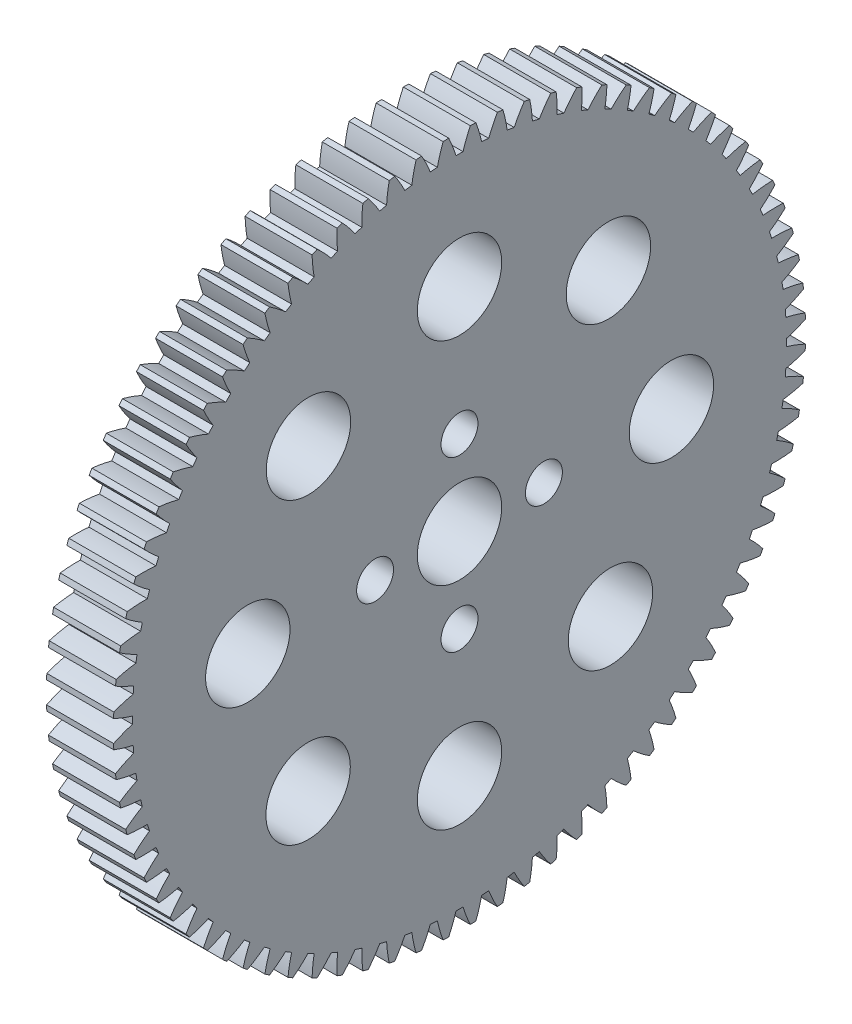
SolidWorks part; units mm, degrees
material "2024 Alloy"
ref_plane "Front Plane" through (0, 0, 0) normal (0, 0, 1) x (1, 0, 0)
ref_plane "Top Plane" through (0, 0, 0) normal (0, 1, 0) x (1, 0, 0)
ref_plane "Right Plane" through (0, 0, 0) normal (1, 0, 0) x (0, 0, -1)
ref_plane "Plane1" through (0, 0, 0) normal (-1, 0, 0) x (0, -1, 0)
ref_axis "Axis1" through (-3.4925, 0, 0) along (1, 0, 0)
sketch "Sketch1" plane through (0, 0, 0) normal (-1, 0, 0) x (0, -1, 0)
  circle A0 centre (0, 0) radius 4
  circle A1 centre (0, 8) radius 1.75
  circle A2 centre (-20.084, 0) radius 4
  circle A3 centre (20.0633, 0) radius 4
  circle A4 centre (0, -20.084) radius 4
  circle A5 centre (0, 20.0633) radius 4
  circle A6 centre (-14.3663, -14.1126) radius 4
  circle A7 centre (14.142, -14.3069) radius 4
  circle A8 centre (14.1351, 14.3483) radius 4
  circle A9 centre (-14.1597, 14.315) radius 4
  circle A10 centre (-8, 0) radius 1.75
  circle A11 centre (8, 0) radius 1.75
  circle A12 centre (0, -8) radius 1.75
  arc A13 (-32.5405, -4.1179) -> (-30.6681, -4.5175) centre (-28.9403, 8.1654) ccw
  arc A14 (-30.6681, -4.5175) -> (-30.563, -5.1806) centre (0, 0) ccw
  arc A15 (-30.563, -5.1806) -> (-32.2203, -6.1392) centre (-25.0006, -16.7088) ccw
  arc A16 (-32.2203, -6.1392) -> (-32.1171, -6.6583) centre (0, 0) ccw
  arc A17 (-32.1171, -6.6583) -> (-30.2191, -6.9097) centre (-29.4917, 5.8696) ccw
  arc A18 (-30.2191, -6.9097) -> (-30.0624, -7.5626) centre (0, 0) ccw
  arc A19 (-30.0624, -7.5626) -> (-31.6393, -8.6483) centre (-23.6126, -18.6188) ccw
  arc A20 (-31.6393, -8.6483) -> (-31.4957, -9.1576) centre (0, 0) ccw
  arc A21 (-31.4957, -9.1576) -> (-29.5838, -9.2594) centre (-29.8613, 3.5376) ccw
  arc A22 (-29.5838, -9.2594) -> (-29.3763, -9.8979) centre (0, 0) ccw
  arc A23 (-29.3763, -9.8979) -> (-30.8633, -11.104) centre (-22.079, -20.414) ccw
  arc A24 (-30.8633, -11.104) -> (-30.6801, -11.6005) centre (0, 0) ccw
  arc A25 (-30.6801, -11.6005) -> (-28.7661, -11.552) centre (-30.0469, 1.1838) ccw
  arc A26 (-28.7661, -11.552) -> (-28.5092, -12.1723) centre (0, 0) ccw
  arc A27 (-28.5092, -12.1723) -> (-29.8969, -13.4913) centre (-20.4093, -22.0834) ccw
  arc A28 (-29.8969, -13.4913) -> (-29.6753, -13.9719) centre (0, 0) ccw
  arc A29 (-29.6753, -13.9719) -> (-27.7711, -13.7733) centre (-30.0471, -1.1773) ccw
  arc A30 (-27.7711, -13.7733) -> (-27.4663, -14.3715) centre (0, 0) ccw
  arc A31 (-27.4663, -14.3715) -> (-28.7462, -15.7954) centre (-18.6137, -23.6166) ccw
  arc A32 (-28.7462, -15.7954) -> (-28.4876, -16.2571) centre (0, 0) ccw
  arc A33 (-28.4876, -16.2571) -> (-26.6048, -15.9097) centre (-29.8621, -3.5311) ccw
  arc A34 (-26.6048, -15.9097) -> (-26.254, -16.4822) centre (0, 0) ccw
  arc A35 (-26.254, -16.4822) -> (-27.4183, -18.0021) centre (-16.7034, -25.0042) ccw
  arc A36 (-27.4183, -18.0021) -> (-27.1243, -18.4421) centre (0, 0) ccw
  arc A37 (-27.1243, -18.4421) -> (-25.2746, -17.9481) centre (-29.493, -5.8632) ccw
  arc A38 (-25.2746, -17.9481) -> (-24.8799, -18.4913) centre (0, 0) ccw
  arc A39 (-24.8799, -18.4913) -> (-25.9214, -20.0978) centre (-14.6901, -26.2377) ccw
  arc A40 (-25.9214, -20.0978) -> (-25.5937, -20.5134) centre (0, 0) ccw
  arc A41 (-25.5937, -20.5134) -> (-23.7885, -19.8758) centre (-28.9421, -8.1591) ccw
  arc A42 (-23.7885, -19.8758) -> (-23.3524, -20.3863) centre (0, 0) ccw
  arc A43 (-23.3524, -20.3863) -> (-24.2646, -22.0696) centre (-12.5862, -27.3094) ccw
  arc A44 (-24.2646, -22.0696) -> (-23.9054, -22.4582) centre (0, 0) ccw
  arc A45 (-23.9054, -22.4582) -> (-22.1557, -21.6809) centre (-28.2127, -10.4047) ccw
  arc A46 (-22.1557, -21.6809) -> (-21.6809, -22.1557) centre (0, 0) ccw
  arc A47 (-21.6809, -22.1557) -> (-22.4582, -23.9054) centre (-10.4047, -28.2127) ccw
  arc A48 (-22.4582, -23.9054) -> (-22.0696, -24.2646) centre (0, 0) ccw
  arc A49 (-22.0696, -24.2646) -> (-20.3863, -23.3524) centre (-27.3094, -12.5862) ccw
  arc A50 (-20.3863, -23.3524) -> (-19.8758, -23.7885) centre (0, 0) ccw
  arc A51 (-19.8758, -23.7885) -> (-20.5134, -25.5937) centre (-8.1591, -28.9421) ccw
  arc A52 (-20.5134, -25.5937) -> (-20.0978, -25.9214) centre (0, 0) ccw
  arc A53 (-20.0978, -25.9214) -> (-18.4913, -24.8799) centre (-26.2377, -14.6901) ccw
  arc A54 (-18.4913, -24.8799) -> (-17.9481, -25.2746) centre (0, 0) ccw
  arc A55 (-17.9481, -25.2746) -> (-18.4421, -27.1243) centre (-5.8632, -29.493) ccw
  arc A56 (-18.4421, -27.1243) -> (-18.0021, -27.4183) centre (0, 0) ccw
  arc A57 (-18.0021, -27.4183) -> (-16.4822, -26.254) centre (-25.0042, -16.7034) ccw
  arc A58 (-16.4822, -26.254) -> (-15.9097, -26.6048) centre (0, 0) ccw
  arc A59 (-15.9097, -26.6048) -> (-16.2571, -28.4876) centre (-3.5311, -29.8621) ccw
  arc A60 (-16.2571, -28.4876) -> (-15.7954, -28.7462) centre (0, 0) ccw
  arc A61 (-15.7954, -28.7462) -> (-14.3715, -27.4663) centre (-23.6166, -18.6137) ccw
  arc A62 (-14.3715, -27.4663) -> (-13.7733, -27.7711) centre (0, 0) ccw
  arc A63 (-13.7733, -27.7711) -> (-13.9719, -29.6753) centre (-1.1773, -30.0471) ccw
  arc A64 (-13.9719, -29.6753) -> (-13.4913, -29.8969) centre (0, 0) ccw
  arc A65 (-13.4913, -29.8969) -> (-12.1723, -28.5092) centre (-22.0834, -20.4093) ccw
  arc A66 (-12.1723, -28.5092) -> (-11.552, -28.7661) centre (0, 0) ccw
  arc A67 (-11.552, -28.7661) -> (-11.6005, -30.6801) centre (1.1838, -30.0469) ccw
  arc A68 (-11.6005, -30.6801) -> (-11.104, -30.8633) centre (0, 0) ccw
  arc A69 (-11.104, -30.8633) -> (-9.8979, -29.3763) centre (-20.414, -22.079) ccw
  arc A70 (-9.8979, -29.3763) -> (-9.2594, -29.5838) centre (0, 0) ccw
  arc A71 (-9.2594, -29.5838) -> (-9.1576, -31.4957) centre (3.5376, -29.8613) ccw
  arc A72 (-9.1576, -31.4957) -> (-8.6483, -31.6393) centre (0, 0) ccw
  arc A73 (-8.6483, -31.6393) -> (-7.5626, -30.0624) centre (-18.6188, -23.6126) ccw
  arc A74 (-7.5626, -30.0624) -> (-6.9097, -30.2191) centre (0, 0) ccw
  arc A75 (-6.9097, -30.2191) -> (-6.6583, -32.1171) centre (5.8696, -29.4917) ccw
  arc A76 (-6.6583, -32.1171) -> (-6.1392, -32.2203) centre (0, 0) ccw
  arc A77 (-6.1392, -32.2203) -> (-5.1806, -30.563) centre (-16.7088, -25.0006) ccw
  arc A78 (-5.1806, -30.563) -> (-4.5175, -30.6681) centre (0, 0) ccw
  arc A79 (-4.5175, -30.6681) -> (-4.1179, -32.5405) centre (8.1654, -28.9403) ccw
  arc A80 (-4.1179, -32.5405) -> (-3.5923, -32.6027) centre (0, 0) ccw
  arc A81 (-3.5923, -32.6027) -> (-2.7667, -30.8753) centre (-14.6958, -26.2345) ccw
  arc A82 (-2.7667, -30.8753) -> (-2.0973, -30.928) centre (0, 0) ccw
  arc A83 (-2.0973, -30.928) -> (-1.5521, -32.7633) centre (10.4109, -28.2104) ccw
  arc A84 (-1.5521, -32.7633) -> (-1.0233, -32.784) centre (0, 0) ccw
  arc A85 (-1.0233, -32.784) -> (-0.3357, -30.9972) centre (-12.5921, -27.3066) ccw
  arc A86 (-0.3357, -30.9972) -> (0.3357, -30.9972) centre (0, 0) ccw
  arc A87 (0.3357, -30.9972) -> (1.0233, -32.784) centre (12.5921, -27.3066) ccw
  arc A88 (1.0233, -32.784) -> (1.5521, -32.7633) centre (0, 0) ccw
  arc A89 (1.5521, -32.7633) -> (2.0973, -30.928) centre (-10.4109, -28.2104) ccw
  arc A90 (2.0973, -30.928) -> (2.7667, -30.8753) centre (0, 0) ccw
  arc A91 (2.7667, -30.8753) -> (3.5923, -32.6027) centre (14.6958, -26.2345) ccw
  arc A92 (3.5923, -32.6027) -> (4.1179, -32.5405) centre (0, 0) ccw
  arc A93 (4.1179, -32.5405) -> (4.5175, -30.6681) centre (-8.1654, -28.9403) ccw
  arc A94 (4.5175, -30.6681) -> (5.1806, -30.563) centre (0, 0) ccw
  arc A95 (5.1806, -30.563) -> (6.1392, -32.2203) centre (16.7088, -25.0006) ccw
  arc A96 (6.1392, -32.2203) -> (6.6583, -32.1171) centre (0, 0) ccw
  arc A97 (6.6583, -32.1171) -> (6.9097, -30.2191) centre (-5.8696, -29.4917) ccw
  arc A98 (6.9097, -30.2191) -> (7.5626, -30.0624) centre (0, 0) ccw
  arc A99 (7.5626, -30.0624) -> (8.6483, -31.6393) centre (18.6188, -23.6126) ccw
  arc A100 (8.6483, -31.6393) -> (9.1576, -31.4957) centre (0, 0) ccw
  arc A101 (9.1576, -31.4957) -> (9.2594, -29.5838) centre (-3.5376, -29.8613) ccw
  arc A102 (9.2594, -29.5838) -> (9.8979, -29.3763) centre (0, 0) ccw
  arc A103 (9.8979, -29.3763) -> (11.104, -30.8633) centre (20.414, -22.079) ccw
  arc A104 (11.104, -30.8633) -> (11.6005, -30.6801) centre (0, 0) ccw
  arc A105 (11.6005, -30.6801) -> (11.552, -28.7661) centre (-1.1838, -30.0469) ccw
  arc A106 (11.552, -28.7661) -> (12.1723, -28.5092) centre (0, 0) ccw
  arc A107 (12.1723, -28.5092) -> (13.4913, -29.8969) centre (22.0834, -20.4093) ccw
  arc A108 (13.4913, -29.8969) -> (13.9719, -29.6753) centre (0, 0) ccw
  arc A109 (13.9719, -29.6753) -> (13.7733, -27.7711) centre (1.1773, -30.0471) ccw
  arc A110 (13.7733, -27.7711) -> (14.3715, -27.4663) centre (0, 0) ccw
  arc A111 (14.3715, -27.4663) -> (15.7954, -28.7462) centre (23.6166, -18.6137) ccw
  arc A112 (15.7954, -28.7462) -> (16.2571, -28.4876) centre (0, 0) ccw
  arc A113 (16.2571, -28.4876) -> (15.9097, -26.6048) centre (3.5311, -29.8621) ccw
  arc A114 (15.9097, -26.6048) -> (16.4822, -26.254) centre (0, 0) ccw
  arc A115 (16.4822, -26.254) -> (18.0021, -27.4183) centre (25.0042, -16.7034) ccw
  arc A116 (18.0021, -27.4183) -> (18.4421, -27.1243) centre (0, 0) ccw
  arc A117 (18.4421, -27.1243) -> (17.9481, -25.2746) centre (5.8632, -29.493) ccw
  arc A118 (17.9481, -25.2746) -> (18.4913, -24.8799) centre (0, 0) ccw
  arc A119 (18.4913, -24.8799) -> (20.0978, -25.9214) centre (26.2377, -14.6901) ccw
  arc A120 (20.0978, -25.9214) -> (20.5134, -25.5937) centre (0, 0) ccw
  arc A121 (20.5134, -25.5937) -> (19.8758, -23.7885) centre (8.1591, -28.9421) ccw
  arc A122 (19.8758, -23.7885) -> (20.3863, -23.3524) centre (0, 0) ccw
  arc A123 (20.3863, -23.3524) -> (22.0696, -24.2646) centre (27.3094, -12.5862) ccw
  arc A124 (22.0696, -24.2646) -> (22.4582, -23.9054) centre (0, 0) ccw
  arc A125 (22.4582, -23.9054) -> (21.6809, -22.1557) centre (10.4047, -28.2127) ccw
  arc A126 (21.6809, -22.1557) -> (22.1557, -21.6809) centre (0, 0) ccw
  arc A127 (22.1557, -21.6809) -> (23.9054, -22.4582) centre (28.2127, -10.4047) ccw
  arc A128 (23.9054, -22.4582) -> (24.2646, -22.0696) centre (0, 0) ccw
  arc A129 (24.2646, -22.0696) -> (23.3524, -20.3863) centre (12.5862, -27.3094) ccw
  arc A130 (23.3524, -20.3863) -> (23.7885, -19.8758) centre (0, 0) ccw
  arc A131 (23.7885, -19.8758) -> (25.5937, -20.5134) centre (28.9421, -8.1591) ccw
  arc A132 (25.5937, -20.5134) -> (25.9214, -20.0978) centre (0, 0) ccw
  arc A133 (25.9214, -20.0978) -> (24.8799, -18.4913) centre (14.6901, -26.2377) ccw
  arc A134 (24.8799, -18.4913) -> (25.2746, -17.9481) centre (0, 0) ccw
  arc A135 (25.2746, -17.9481) -> (27.1243, -18.4421) centre (29.493, -5.8632) ccw
  arc A136 (27.1243, -18.4421) -> (27.4183, -18.0021) centre (0, 0) ccw
  arc A137 (27.4183, -18.0021) -> (26.254, -16.4822) centre (16.7034, -25.0042) ccw
  arc A138 (26.254, -16.4822) -> (26.6048, -15.9097) centre (0, 0) ccw
  arc A139 (26.6048, -15.9097) -> (28.4876, -16.2571) centre (29.8621, -3.5311) ccw
  arc A140 (28.4876, -16.2571) -> (28.7462, -15.7954) centre (0, 0) ccw
  arc A141 (28.7462, -15.7954) -> (27.4663, -14.3715) centre (18.6137, -23.6166) ccw
  arc A142 (27.4663, -14.3715) -> (27.7711, -13.7733) centre (0, 0) ccw
  arc A143 (27.7711, -13.7733) -> (29.6753, -13.9719) centre (30.0471, -1.1773) ccw
  arc A144 (29.6753, -13.9719) -> (29.8969, -13.4913) centre (0, 0) ccw
  arc A145 (29.8969, -13.4913) -> (28.5092, -12.1723) centre (20.4093, -22.0834) ccw
  arc A146 (28.5092, -12.1723) -> (28.7661, -11.552) centre (0, 0) ccw
  arc A147 (28.7661, -11.552) -> (30.6801, -11.6005) centre (30.0469, 1.1838) ccw
  arc A148 (30.6801, -11.6005) -> (30.8633, -11.104) centre (0, 0) ccw
  arc A149 (30.8633, -11.104) -> (29.3763, -9.8979) centre (22.079, -20.414) ccw
  arc A150 (29.3763, -9.8979) -> (29.5838, -9.2594) centre (0, 0) ccw
  arc A151 (29.5838, -9.2594) -> (31.4957, -9.1576) centre (29.8613, 3.5376) ccw
  arc A152 (31.4957, -9.1576) -> (31.6393, -8.6483) centre (0, 0) ccw
  arc A153 (31.6393, -8.6483) -> (30.0624, -7.5626) centre (23.6126, -18.6188) ccw
  arc A154 (30.0624, -7.5626) -> (30.2191, -6.9097) centre (0, 0) ccw
  arc A155 (30.2191, -6.9097) -> (32.1171, -6.6583) centre (29.4917, 5.8696) ccw
  arc A156 (32.1171, -6.6583) -> (32.2203, -6.1392) centre (0, 0) ccw
  arc A157 (32.2203, -6.1392) -> (30.563, -5.1806) centre (25.0006, -16.7088) ccw
  arc A158 (30.563, -5.1806) -> (30.6681, -4.5175) centre (0, 0) ccw
  arc A159 (30.6681, -4.5175) -> (32.5405, -4.1179) centre (28.9403, 8.1654) ccw
  arc A160 (32.5405, -4.1179) -> (32.6027, -3.5923) centre (0, 0) ccw
  arc A161 (32.6027, -3.5923) -> (30.8753, -2.7667) centre (26.2345, -14.6958) ccw
  arc A162 (30.8753, -2.7667) -> (30.928, -2.0973) centre (0, 0) ccw
  arc A163 (30.928, -2.0973) -> (32.7633, -1.5521) centre (28.2104, 10.4109) ccw
  arc A164 (32.7633, -1.5521) -> (32.784, -1.0233) centre (0, 0) ccw
  arc A165 (32.784, -1.0233) -> (30.9972, -0.3357) centre (27.3066, -12.5921) ccw
  arc A166 (30.9972, -0.3357) -> (30.9972, 0.3357) centre (0, 0) ccw
  arc A167 (30.9972, 0.3357) -> (32.784, 1.0233) centre (27.3066, 12.5921) ccw
  arc A168 (32.784, 1.0233) -> (32.7633, 1.5521) centre (0, 0) ccw
  arc A169 (32.7633, 1.5521) -> (30.928, 2.0973) centre (28.2104, -10.4109) ccw
  arc A170 (30.928, 2.0973) -> (30.8753, 2.7667) centre (0, 0) ccw
  arc A171 (30.8753, 2.7667) -> (32.6027, 3.5923) centre (26.2345, 14.6958) ccw
  arc A172 (32.6027, 3.5923) -> (32.5405, 4.1179) centre (0, 0) ccw
  arc A173 (32.5405, 4.1179) -> (30.6681, 4.5175) centre (28.9403, -8.1654) ccw
  arc A174 (30.6681, 4.5175) -> (30.563, 5.1806) centre (0, 0) ccw
  arc A175 (30.563, 5.1806) -> (32.2203, 6.1392) centre (25.0006, 16.7088) ccw
  arc A176 (32.2203, 6.1392) -> (32.1171, 6.6583) centre (0, 0) ccw
  arc A177 (32.1171, 6.6583) -> (30.2191, 6.9097) centre (29.4917, -5.8696) ccw
  arc A178 (30.2191, 6.9097) -> (30.0624, 7.5626) centre (0, 0) ccw
  arc A179 (30.0624, 7.5626) -> (31.6393, 8.6483) centre (23.6126, 18.6188) ccw
  arc A180 (31.6393, 8.6483) -> (31.4957, 9.1576) centre (0, 0) ccw
  arc A181 (31.4957, 9.1576) -> (29.5838, 9.2594) centre (29.8613, -3.5376) ccw
  arc A182 (29.5838, 9.2594) -> (29.3763, 9.8979) centre (0, 0) ccw
  arc A183 (29.3763, 9.8979) -> (30.8633, 11.104) centre (22.079, 20.414) ccw
  arc A184 (30.8633, 11.104) -> (30.6801, 11.6005) centre (0, 0) ccw
  arc A185 (30.6801, 11.6005) -> (28.7661, 11.552) centre (30.0469, -1.1838) ccw
  arc A186 (28.7661, 11.552) -> (28.5092, 12.1723) centre (0, 0) ccw
  arc A187 (28.5092, 12.1723) -> (29.8969, 13.4913) centre (20.4093, 22.0834) ccw
  arc A188 (29.8969, 13.4913) -> (29.6753, 13.9719) centre (0, 0) ccw
  arc A189 (29.6753, 13.9719) -> (27.7711, 13.7733) centre (30.0471, 1.1773) ccw
  arc A190 (27.7711, 13.7733) -> (27.4663, 14.3715) centre (0, 0) ccw
  arc A191 (27.4663, 14.3715) -> (28.7462, 15.7954) centre (18.6137, 23.6166) ccw
  arc A192 (28.7462, 15.7954) -> (28.4876, 16.2571) centre (0, 0) ccw
  arc A193 (28.4876, 16.2571) -> (26.6048, 15.9097) centre (29.8621, 3.5311) ccw
  arc A194 (26.6048, 15.9097) -> (26.254, 16.4822) centre (0, 0) ccw
  arc A195 (26.254, 16.4822) -> (27.4183, 18.0021) centre (16.7034, 25.0042) ccw
  arc A196 (27.4183, 18.0021) -> (27.1243, 18.4421) centre (0, 0) ccw
  arc A197 (27.1243, 18.4421) -> (25.2746, 17.9481) centre (29.493, 5.8632) ccw
  arc A198 (25.2746, 17.9481) -> (24.8799, 18.4913) centre (0, 0) ccw
  arc A199 (24.8799, 18.4913) -> (25.9214, 20.0978) centre (14.6901, 26.2377) ccw
  arc A200 (25.9214, 20.0978) -> (25.5937, 20.5134) centre (0, 0) ccw
  arc A201 (25.5937, 20.5134) -> (23.7885, 19.8758) centre (28.9421, 8.1591) ccw
  arc A202 (23.7885, 19.8758) -> (23.3524, 20.3863) centre (0, 0) ccw
  arc A203 (23.3524, 20.3863) -> (24.2646, 22.0696) centre (12.5862, 27.3094) ccw
  arc A204 (24.2646, 22.0696) -> (23.9054, 22.4582) centre (0, 0) ccw
  arc A205 (23.9054, 22.4582) -> (22.1557, 21.6809) centre (28.2127, 10.4047) ccw
  arc A206 (22.1557, 21.6809) -> (21.6809, 22.1557) centre (0, 0) ccw
  arc A207 (21.6809, 22.1557) -> (22.4582, 23.9054) centre (10.4047, 28.2127) ccw
  arc A208 (22.4582, 23.9054) -> (22.0696, 24.2646) centre (0, 0) ccw
  arc A209 (22.0696, 24.2646) -> (20.3863, 23.3524) centre (27.3094, 12.5862) ccw
  arc A210 (20.3863, 23.3524) -> (19.8758, 23.7885) centre (0, 0) ccw
  arc A211 (19.8758, 23.7885) -> (20.5134, 25.5937) centre (8.1591, 28.9421) ccw
  arc A212 (20.5134, 25.5937) -> (20.0978, 25.9214) centre (0, 0) ccw
  arc A213 (20.0978, 25.9214) -> (18.4913, 24.8799) centre (26.2377, 14.6901) ccw
  arc A214 (18.4913, 24.8799) -> (17.9481, 25.2746) centre (0, 0) ccw
  arc A215 (17.9481, 25.2746) -> (18.4421, 27.1243) centre (5.8632, 29.493) ccw
  arc A216 (18.4421, 27.1243) -> (18.0021, 27.4183) centre (0, 0) ccw
  arc A217 (18.0021, 27.4183) -> (16.4822, 26.254) centre (25.0042, 16.7034) ccw
  arc A218 (16.4822, 26.254) -> (15.9097, 26.6048) centre (0, 0) ccw
  arc A219 (15.9097, 26.6048) -> (16.2571, 28.4876) centre (3.5311, 29.8621) ccw
  arc A220 (16.2571, 28.4876) -> (15.7954, 28.7462) centre (0, 0) ccw
  arc A221 (15.7954, 28.7462) -> (14.3715, 27.4663) centre (23.6166, 18.6137) ccw
  arc A222 (14.3715, 27.4663) -> (13.7733, 27.7711) centre (0, 0) ccw
  arc A223 (13.7733, 27.7711) -> (13.9719, 29.6753) centre (1.1773, 30.0471) ccw
  arc A224 (13.9719, 29.6753) -> (13.4913, 29.8969) centre (0, 0) ccw
  arc A225 (13.4913, 29.8969) -> (12.1723, 28.5092) centre (22.0834, 20.4093) ccw
  arc A226 (12.1723, 28.5092) -> (11.552, 28.7661) centre (0, 0) ccw
  arc A227 (11.552, 28.7661) -> (11.6005, 30.6801) centre (-1.1838, 30.0469) ccw
  arc A228 (11.6005, 30.6801) -> (11.104, 30.8633) centre (0, 0) ccw
  arc A229 (11.104, 30.8633) -> (9.8979, 29.3763) centre (20.414, 22.079) ccw
  arc A230 (9.8979, 29.3763) -> (9.2594, 29.5838) centre (0, 0) ccw
  arc A231 (9.2594, 29.5838) -> (9.1576, 31.4957) centre (-3.5376, 29.8613) ccw
  arc A232 (9.1576, 31.4957) -> (8.6483, 31.6393) centre (0, 0) ccw
  arc A233 (8.6483, 31.6393) -> (7.5626, 30.0624) centre (18.6188, 23.6126) ccw
  arc A234 (7.5626, 30.0624) -> (6.9097, 30.2191) centre (0, 0) ccw
  arc A235 (6.9097, 30.2191) -> (6.6583, 32.1171) centre (-5.8696, 29.4917) ccw
  arc A236 (6.6583, 32.1171) -> (6.1392, 32.2203) centre (0, 0) ccw
  arc A237 (6.1392, 32.2203) -> (5.1806, 30.563) centre (16.7088, 25.0006) ccw
  arc A238 (5.1806, 30.563) -> (4.5175, 30.6681) centre (0, 0) ccw
  arc A239 (4.5175, 30.6681) -> (4.1179, 32.5405) centre (-8.1654, 28.9403) ccw
  arc A240 (4.1179, 32.5405) -> (3.5923, 32.6027) centre (0, 0) ccw
  arc A241 (3.5923, 32.6027) -> (2.7667, 30.8753) centre (14.6958, 26.2345) ccw
  arc A242 (2.7667, 30.8753) -> (2.0973, 30.928) centre (0, 0) ccw
  arc A243 (2.0973, 30.928) -> (1.5521, 32.7633) centre (-10.4109, 28.2104) ccw
  arc A244 (1.5521, 32.7633) -> (1.0233, 32.784) centre (0, 0) ccw
  arc A245 (1.0233, 32.784) -> (0.3357, 30.9972) centre (12.5921, 27.3066) ccw
  arc A246 (0.3357, 30.9972) -> (-0.3357, 30.9972) centre (0, 0) ccw
  arc A247 (-0.3357, 30.9972) -> (-1.0233, 32.784) centre (-12.5921, 27.3066) ccw
  arc A248 (-1.0233, 32.784) -> (-1.5521, 32.7633) centre (0, 0) ccw
  arc A249 (-1.5521, 32.7633) -> (-2.0973, 30.928) centre (10.4109, 28.2104) ccw
  arc A250 (-2.0973, 30.928) -> (-2.7667, 30.8753) centre (0, 0) ccw
  arc A251 (-2.7667, 30.8753) -> (-3.5923, 32.6027) centre (-14.6958, 26.2345) ccw
  arc A252 (-3.5923, 32.6027) -> (-4.1179, 32.5405) centre (0, 0) ccw
  arc A253 (-4.1179, 32.5405) -> (-4.5175, 30.6681) centre (8.1654, 28.9403) ccw
  arc A254 (-4.5175, 30.6681) -> (-5.1806, 30.563) centre (0, 0) ccw
  arc A255 (-5.1806, 30.563) -> (-6.1392, 32.2203) centre (-16.7088, 25.0006) ccw
  arc A256 (-6.1392, 32.2203) -> (-6.6583, 32.1171) centre (0, 0) ccw
  arc A257 (-6.6583, 32.1171) -> (-6.9097, 30.2191) centre (5.8696, 29.4917) ccw
  arc A258 (-6.9097, 30.2191) -> (-7.5626, 30.0624) centre (0, 0) ccw
  arc A259 (-7.5626, 30.0624) -> (-8.6483, 31.6393) centre (-18.6188, 23.6126) ccw
  arc A260 (-8.6483, 31.6393) -> (-9.1576, 31.4957) centre (0, 0) ccw
  arc A261 (-9.1576, 31.4957) -> (-9.2594, 29.5838) centre (3.5376, 29.8613) ccw
  arc A262 (-9.2594, 29.5838) -> (-9.8979, 29.3763) centre (0, 0) ccw
  arc A263 (-9.8979, 29.3763) -> (-11.104, 30.8633) centre (-20.414, 22.079) ccw
  arc A264 (-11.104, 30.8633) -> (-11.6005, 30.6801) centre (0, 0) ccw
  arc A265 (-11.6005, 30.6801) -> (-11.552, 28.7661) centre (1.1838, 30.0469) ccw
  arc A266 (-11.552, 28.7661) -> (-12.1723, 28.5092) centre (0, 0) ccw
  arc A267 (-12.1723, 28.5092) -> (-13.4913, 29.8969) centre (-22.0834, 20.4093) ccw
  arc A268 (-13.4913, 29.8969) -> (-13.9719, 29.6753) centre (0, 0) ccw
  arc A269 (-13.9719, 29.6753) -> (-13.7733, 27.7711) centre (-1.1773, 30.0471) ccw
  arc A270 (-13.7733, 27.7711) -> (-14.3715, 27.4663) centre (0, 0) ccw
  arc A271 (-14.3715, 27.4663) -> (-15.7954, 28.7462) centre (-23.6166, 18.6137) ccw
  arc A272 (-15.7954, 28.7462) -> (-16.2571, 28.4876) centre (0, 0) ccw
  arc A273 (-16.2571, 28.4876) -> (-15.9097, 26.6048) centre (-3.5311, 29.8621) ccw
  arc A274 (-15.9097, 26.6048) -> (-16.4822, 26.254) centre (0, 0) ccw
  arc A275 (-16.4822, 26.254) -> (-18.0021, 27.4183) centre (-25.0042, 16.7034) ccw
  arc A276 (-18.0021, 27.4183) -> (-18.4421, 27.1243) centre (0, 0) ccw
  arc A277 (-18.4421, 27.1243) -> (-17.9481, 25.2746) centre (-5.8632, 29.493) ccw
  arc A278 (-17.9481, 25.2746) -> (-18.4913, 24.8799) centre (0, 0) ccw
  arc A279 (-18.4913, 24.8799) -> (-20.0978, 25.9214) centre (-26.2377, 14.6901) ccw
  arc A280 (-20.0978, 25.9214) -> (-20.5134, 25.5937) centre (0, 0) ccw
  arc A281 (-20.5134, 25.5937) -> (-19.8758, 23.7885) centre (-8.1591, 28.9421) ccw
  arc A282 (-19.8758, 23.7885) -> (-20.3863, 23.3524) centre (0, 0) ccw
  arc A283 (-20.3863, 23.3524) -> (-22.0696, 24.2646) centre (-27.3094, 12.5862) ccw
  arc A284 (-22.0696, 24.2646) -> (-22.4582, 23.9054) centre (0, 0) ccw
  arc A285 (-22.4582, 23.9054) -> (-21.6809, 22.1557) centre (-10.4047, 28.2127) ccw
  arc A286 (-21.6809, 22.1557) -> (-22.1557, 21.6809) centre (0, 0) ccw
  arc A287 (-22.1557, 21.6809) -> (-23.9054, 22.4582) centre (-28.2127, 10.4047) ccw
  arc A288 (-23.9054, 22.4582) -> (-24.2646, 22.0696) centre (0, 0) ccw
  arc A289 (-24.2646, 22.0696) -> (-23.3524, 20.3863) centre (-12.5862, 27.3094) ccw
  arc A290 (-23.3524, 20.3863) -> (-23.7885, 19.8758) centre (0, 0) ccw
  arc A291 (-23.7885, 19.8758) -> (-25.5937, 20.5134) centre (-28.9421, 8.1591) ccw
  arc A292 (-25.5937, 20.5134) -> (-25.9214, 20.0978) centre (0, 0) ccw
  arc A293 (-25.9214, 20.0978) -> (-24.8799, 18.4913) centre (-14.6901, 26.2377) ccw
  arc A294 (-24.8799, 18.4913) -> (-25.2746, 17.9481) centre (0, 0) ccw
  arc A295 (-25.2746, 17.9481) -> (-27.1243, 18.4421) centre (-29.493, 5.8632) ccw
  arc A296 (-27.1243, 18.4421) -> (-27.4183, 18.0021) centre (0, 0) ccw
  arc A297 (-27.4183, 18.0021) -> (-26.254, 16.4822) centre (-16.7034, 25.0042) ccw
  arc A298 (-26.254, 16.4822) -> (-26.6048, 15.9097) centre (0, 0) ccw
  arc A299 (-26.6048, 15.9097) -> (-28.4876, 16.2571) centre (-29.8621, 3.5311) ccw
  arc A300 (-28.4876, 16.2571) -> (-28.7462, 15.7954) centre (0, 0) ccw
  arc A301 (-28.7462, 15.7954) -> (-27.4663, 14.3715) centre (-18.6137, 23.6166) ccw
  arc A302 (-27.4663, 14.3715) -> (-27.7711, 13.7733) centre (0, 0) ccw
  arc A303 (-27.7711, 13.7733) -> (-29.6753, 13.9719) centre (-30.0471, 1.1773) ccw
  arc A304 (-29.6753, 13.9719) -> (-29.8969, 13.4913) centre (0, 0) ccw
  arc A305 (-29.8969, 13.4913) -> (-28.5092, 12.1723) centre (-20.4093, 22.0834) ccw
  arc A306 (-28.5092, 12.1723) -> (-28.7661, 11.552) centre (0, 0) ccw
  arc A307 (-28.7661, 11.552) -> (-30.6801, 11.6005) centre (-30.0469, -1.1838) ccw
  arc A308 (-30.6801, 11.6005) -> (-30.8633, 11.104) centre (0, 0) ccw
  arc A309 (-30.8633, 11.104) -> (-29.3763, 9.8979) centre (-22.079, 20.414) ccw
  arc A310 (-29.3763, 9.8979) -> (-29.5838, 9.2594) centre (0, 0) ccw
  arc A311 (-29.5838, 9.2594) -> (-31.4957, 9.1576) centre (-29.8613, -3.5376) ccw
  arc A312 (-31.4957, 9.1576) -> (-31.6393, 8.6483) centre (0, 0) ccw
  arc A313 (-31.6393, 8.6483) -> (-30.0624, 7.5626) centre (-23.6126, 18.6188) ccw
  arc A314 (-30.0624, 7.5626) -> (-30.2191, 6.9097) centre (0, 0) ccw
  arc A315 (-30.2191, 6.9097) -> (-32.1171, 6.6583) centre (-29.4917, -5.8696) ccw
  arc A316 (-32.1171, 6.6583) -> (-32.2203, 6.1392) centre (0, 0) ccw
  arc A317 (-32.2203, 6.1392) -> (-30.563, 5.1806) centre (-25.0006, 16.7088) ccw
  arc A318 (-30.563, 5.1806) -> (-30.6681, 4.5175) centre (0, 0) ccw
  arc A319 (-30.6681, 4.5175) -> (-32.5405, 4.1179) centre (-28.9403, -8.1654) ccw
  arc A320 (-32.5405, 4.1179) -> (-32.6027, 3.5923) centre (0, 0) ccw
  arc A321 (-32.6027, 3.5923) -> (-30.8753, 2.7667) centre (-26.2345, 14.6958) ccw
  arc A322 (-30.8753, 2.7667) -> (-30.928, 2.0973) centre (0, 0) ccw
  arc A323 (-30.928, 2.0973) -> (-32.7633, 1.5521) centre (-28.2104, -10.4109) ccw
  arc A324 (-32.7633, 1.5521) -> (-32.784, 1.0233) centre (0, 0) ccw
  arc A325 (-32.784, 1.0233) -> (-30.9972, 0.3357) centre (-27.3066, 12.5921) ccw
  arc A326 (-30.9972, 0.3357) -> (-30.9972, -0.3357) centre (0, 0) ccw
  arc A327 (-30.9972, -0.3357) -> (-32.784, -1.0233) centre (-27.3066, -12.5921) ccw
  arc A328 (-32.784, -1.0233) -> (-32.7633, -1.5521) centre (0, 0) ccw
  arc A329 (-32.7633, -1.5521) -> (-30.928, -2.0973) centre (-28.2104, 10.4109) ccw
  arc A330 (-30.928, -2.0973) -> (-30.8753, -2.7667) centre (0, 0) ccw
  arc A331 (-30.8753, -2.7667) -> (-32.6027, -3.5923) centre (-26.2345, -14.6958) ccw
  arc A332 (-32.6027, -3.5923) -> (-32.5405, -4.1179) centre (0, 0) ccw
extrude "Boss-Extrude1" add sketch "Sketch1" against normal mid plane 6.35
sketch "Sketch2" plane through (0, 0, 0) normal (1, 0, 0) x (0, 0, -1)
  circle A0 centre (0, 0) radius 32 construction
  dimension "D1" = 64
sketch "Sketch3" [suppressed] plane through (0, 0, 0) normal (1, 0, 0) x (0, 0, -1)
  circle A6 centre (0, 23.8125) radius 1.9939
  circle A7 centre (-20.6222, 11.9063) radius 1.9939
  circle A8 centre (-20.6222, -11.9063) radius 1.9939
  circle A9 centre (0, -23.8125) radius 1.9939
  circle A10 centre (20.6222, -11.9063) radius 1.9939
  circle A11 centre (20.6222, 11.9063) radius 1.9939
